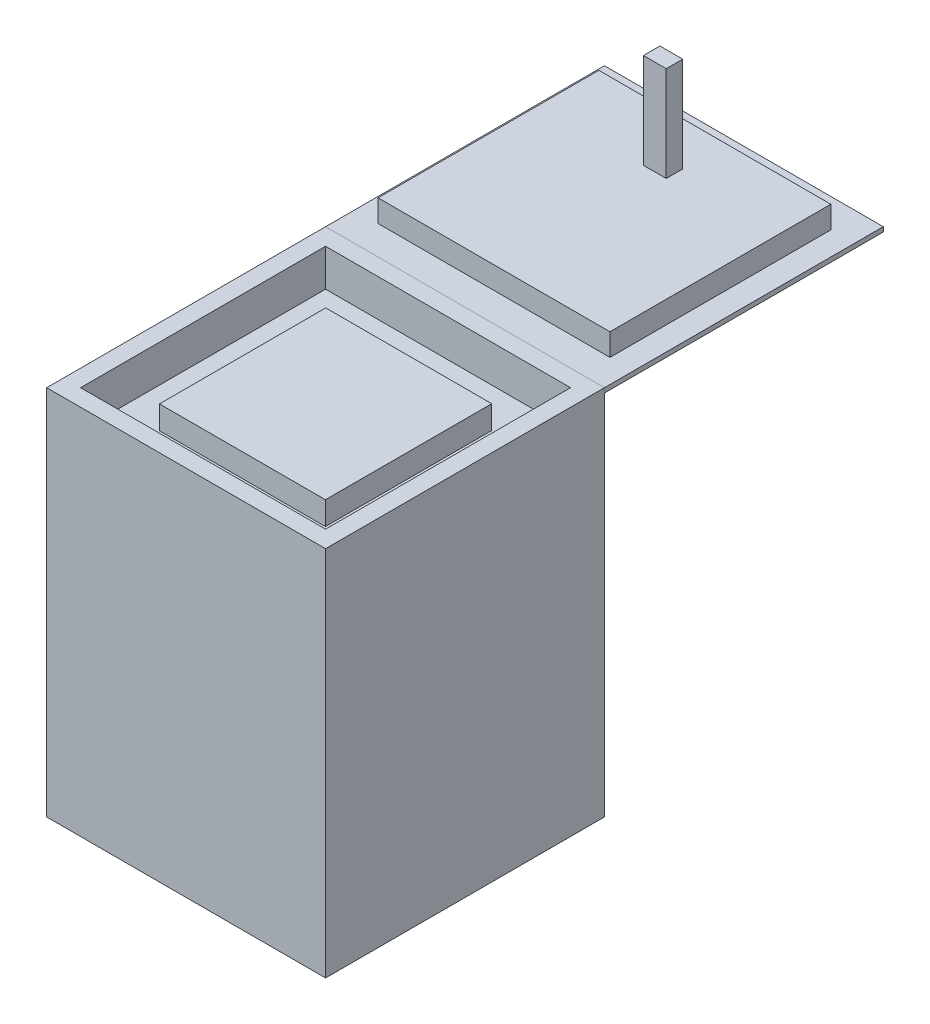
SolidWorks part; units mm, degrees
ref_plane "Front Plane" through (0, 0, 0) normal (0, 0, 1) x (1, 0, 0)
ref_plane "Top Plane" through (0, 0, 0) normal (0, 1, 0) x (1, 0, 0)
ref_plane "Right Plane" through (0, 0, 0) normal (1, 0, 0) x (0, 0, -1)
sketch "Sketch1" plane through (0, 0, 0) normal (0, 1, 0) x (1, 0, 0)
  line L1 (300, 300) -> (-300, 300)
  line L2 (300, 300) -> (300, -300)
  line L3 (300, -300) -> (-300, -300)
  line L4 (-300, 300) -> (-300, -300)
  line L5 (300, 300) -> (-300, -300) construction
  line L6 (300, -300) -> (-300, 300) construction
  point P0 (0, 0)
  dimension "D1" = 600
  dimension "D2" = 600
extrude "Boss-Extrude1" add sketch "Sketch1" along normal blind 800
sketch "Sketch2" plane through (0, 800, 0) normal (0, 1, 0) x (1, 0, 0)
  line L1 (-263.5729, -263.5729) -> (263.5729, -263.5729)
  line L2 (-263.5729, -263.5729) -> (-263.5729, 263.5729)
  line L3 (-263.5729, 263.5729) -> (263.5729, 263.5729)
  line L4 (263.5729, -263.5729) -> (263.5729, 263.5729)
  line L5 (-263.5729, -263.5729) -> (263.5729, 263.5729) construction
  line L6 (-263.5729, 263.5729) -> (263.5729, -263.5729) construction
extrude "Cut-Extrude2" cut sketch "Sketch2" against normal blind 80
sketch "Sketch3" plane through (0, 720, 0) normal (0, 1, 0) x (1, 0, 0)
  line L1 (-178.5595, -178.9117) -> (178.5595, -178.9117)
  line L2 (-178.5595, -178.9117) -> (-178.5595, 178.9117)
  line L3 (-178.5595, 178.9117) -> (178.5595, 178.9117)
  line L4 (178.5595, -178.9117) -> (178.5595, 178.9117)
  line L5 (-178.5595, -178.9117) -> (178.5595, 178.9117) construction
  line L6 (-178.5595, 178.9117) -> (178.5595, -178.9117) construction
extrude "Boss-Extrude2" add sketch "Sketch3" along normal blind 50
sketch "Sketch4" plane through (0, 800, 0) normal (0, 1, 0) x (1, 0, 0)
  line L1 (300, 300) -> (-300, 300)
  line L2 (300, 300) -> (300, 900)
  line L3 (300, 900) -> (-300, 900)
  line L4 (-300, 300) -> (-300, 900)
  dimension "D1" = 600
  dimension "D2" = 600
extrude "Boss-Extrude3" add sketch "Sketch4" against normal blind 10 separate body
sketch "Sketch7" plane through (0, 0, 0) normal (1, 0, 0) x (0, 0, -1)
  line L0 (600, 533.3011) -> (600, 1035.5411) construction
  line L1 (300, 800) -> (300, 0) construction
  line L2 (362.4057, 800) -> (362.4057, 847.8347)
  line L3 (362.4057, 800) -> (837.5943, 800)
  line L5 (362.4057, 847.8347) -> (837.5943, 847.8347)
  line L6 (837.5943, 800) -> (837.5943, 847.8347)
  line L7 (900, 800) -> (300, 800) construction
  dimension "D1" = 300
  dimension "D2" = 47.8347
  dimension "D3" = 0
extrude "Boss-Extrude8" add sketch "Sketch7" along normal mid plane 499 separate body
ref_plane "Plane1" through (0, 540, 0) normal (0, -1, 0) x (-1, 0, 0)
sketch "Sketch15" plane through (0, 0, 0) normal (1, 0, 0) x (0, 0, -1)
  line L1 (743.9858, 847.8347) -> (708.4776, 847.8347)
  line L2 (743.9858, 847.8347) -> (743.9858, 1052.5)
  line L3 (743.9858, 1052.5) -> (708.4776, 1052.5)
  line L4 (708.4776, 847.8347) -> (708.4776, 1052.5)
  line L6 (837.5943, 847.8347) -> (362.4057, 847.8347) construction
  dimension "D1" = 204.6653
  dimension "D2" = 0
extrude "Boss-Extrude9" add sketch "Sketch15" along normal mid plane 49
